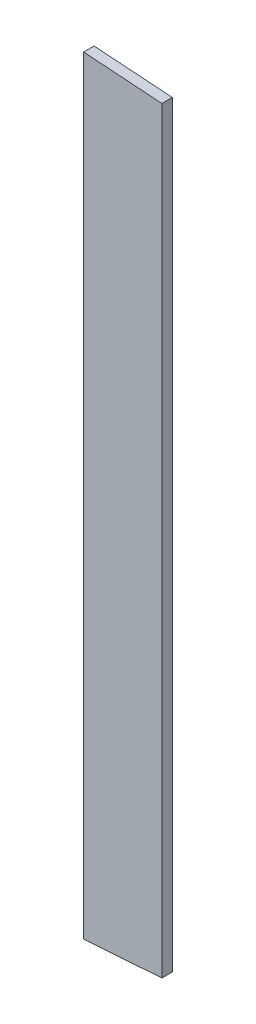
SolidWorks part; units mm, degrees
ref_plane "Front Plane" through (0, 0, 0) normal (0, 0, 1) x (1, 0, 0)
ref_plane "Top Plane" through (0, 0, 0) normal (0, 1, 0) x (1, 0, 0)
ref_plane "Right Plane" through (0, 0, 0) normal (1, 0, 0) x (0, 0, -1)
sketch "Sketch1" plane through (0, 0, 3095.35) normal (0, 0, 1) x (1, 0, 0)
  line L0 (-49.7697, 346.1083) -> (-64.7697, 345.0594)
  line L1 (-140.9262, 339.734) -> (58.5866, 353.6853) construction
  line L2 (-64.7697, 345.0594) -> (-64.7697, 492.4158)
  line L3 (58.5866, 483.7899) -> (-140.9262, 497.7412) construction
  line L4 (-64.7697, 492.4158) -> (-49.7697, 491.3669)
  line L5 (-49.7697, 491.3669) -> (-49.7697, 346.1083)
  dimension "D1" = 15
extrude "Boss-Extrude1" add sketch "Sketch1" along normal blind 2
ref_plane "Plane1" through (-57.2697, 0, 0) normal (1, 0, 0) x (0, 0, -1)
